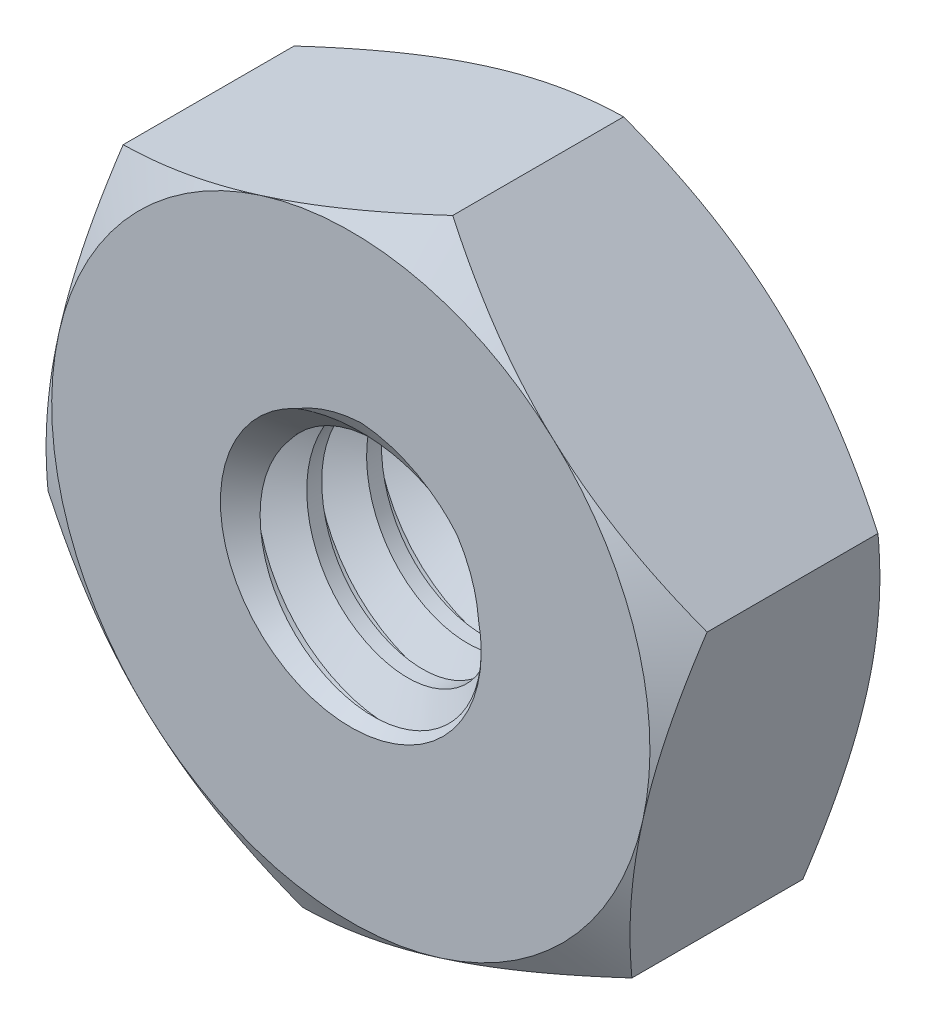
SolidWorks part; units mm, degrees
ref_plane "Front Plane" through (0, 0, 0) normal (0, 0, 1) x (1, 0, 0)
ref_plane "Top Plane" through (0, 0, 0) normal (0, 1, 0) x (1, 0, 0)
ref_plane "Right Plane" through (0, 0, 0) normal (1, 0, 0) x (0, 0, -1)
sketch "Sketch1" plane through (0, 0, 0) normal (0, 0, 1) x (1, 0, 0)
  line L1 (2.7, -2.4801) -> (3.4978, 1.0982)
  line L2 (3.4978, 1.0982) -> (0.7978, 3.5783)
  line L3 (0.7978, 3.5783) -> (-2.7, 2.4801)
  line L4 (-2.7, 2.4801) -> (-3.4978, -1.0982)
  line L5 (-3.4978, -1.0982) -> (-0.7978, -3.5783)
  line L6 (-0.7978, -3.5783) -> (2.7, -2.4801)
  circle A0 centre (0, 0) radius 3.175 construction
  dimension "D1" = 6.35
  dimension "D2" = 0.7978
extrude "Boss-Extrude1" add sketch "Sketch1" along normal blind 2.3813
hole_wizard "Tap Drill for #4-40 Tap1" positions "Sketch15" profile "Sketch16" hole size "#4-40" standard "ANSI Inch" end condition through all
sketch "Sketch15" plane through (0, 0, 0) normal (0, 0, -1) x (-1, 0, 0)
  point P0 (0, 0)
sketch "Sketch16" plane through (0, 0, 0) normal (1, 0, 0) x (0, 1, 0)
  line L0 (0, 0) -> (0, 2.3812)
  line L1 (0, 2.3812) -> (1.1303, 2.3813)
  line L2 (1.1303, 2.3813) -> (1.1303, 0)
  line L5 (1.1303, 0) -> (0, 0)
  line L11 (0, -6.35) -> (0, 107.95) construction
  dimension "Thru Hole Dia." = 2.2606
  dimension "Thru Hole Depth" = 2.3813
sketch "Sketch13" plane through (0, 0, 0) normal (0, 0, -1) x (-1, 0, 0)
  circle A0 centre (0, 0) radius 3.175
  dimension "D1" = 6.35
extrude "Cut-Extrude2" cut sketch "Sketch13" against normal blind 2.3813 draft 60 flip side to cut
sketch "Sketch14" plane through (0, 0, 2.3813) normal (0, 0, 1) x (1, 0, 0)
  line L0 (0, 0) -> (0.7978, 3.5783) construction
  circle A0 centre (0, 0) radius 3.175
  dimension "D1" = 6.35
extrude "Cut-Extrude3" cut sketch "Sketch14" against normal blind 2.3813 draft 60 flip side to cut
chamfer "Chamfer1" distance 0.254 angle 45 2 edges at (-1.1303, 0, 2.3813) (-1.1303, 0, 0)
thread "Thread1" pitch 0.635 method cut profile "Thread Profile1" start angle 0, offset 0.762, length 0, pitch 0.635, diameter 2.2606
ref_plane "Plane1" through (1.1303, 0, -0.508) normal (0, -1, 0) x (1, 0, 0)
sketch "Thread Profile1" plane through (1.1303, 0, -0.508) normal (0, -1, 0) x (1, 0, 0)
  line L0 (0, 0) -> (0, 0.635) construction
  line L1 (0, 0) -> (0.3437, 0.1984)
  line L2 (0.3437, 0.1984) -> (0.3437, 0.2778)
  line L3 (0.3437, 0.2778) -> (0, 0.4762)
  line L4 (0.3437, 0.2381) -> (0, 0.2381) construction
  line L11 (0, 0) -> (0, 0.4762)
  point P2 (0, 0)
  dimension "Pitch" = 0.635
  dimension "Profile_Angle" = 60
  dimension "Profile_Land" = 0.0794
  dimension "Profile_Height" = 0.3437
